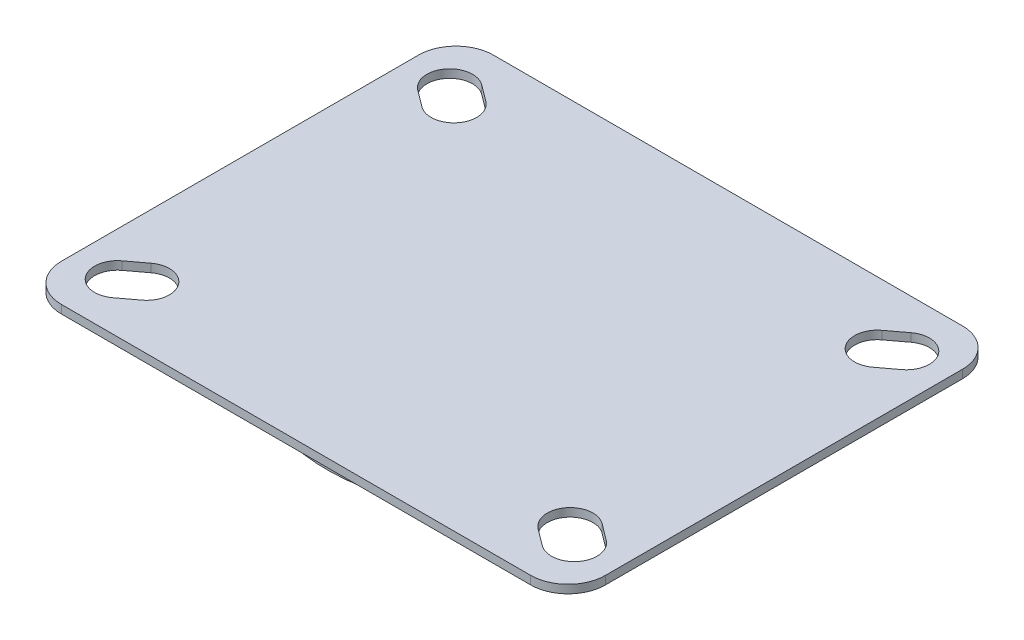
SolidWorks part; units mm, degrees
material "Acero al carbono no aleado"
ref_plane "Alzado" through (0, 0, 0) normal (0, 0, 1) x (1, 0, 0)
ref_plane "Planta" through (0, 0, 0) normal (0, 1, 0) x (1, 0, 0)
ref_plane "Vista lateral" through (0, 0, 0) normal (1, 0, 0) x (0, 0, -1)
sketch "Croquis1" plane through (0, 0, 0) normal (0, 1, 0) x (1, 0, 0)
  line L0 (-54.9902, 40) -> (-50.9902, 37) construction
  line L1 (-56.4956, -52) -> (56.4956, -52)
  line L2 (-65.5, -42.9956) -> (-65.5, 42.9956)
  line L3 (-56.4956, 52) -> (56.4956, 52)
  line L4 (65.5, -42.9956) -> (65.5, 42.9956)
  line L5 (-65.5, -52) -> (65.5, 52) construction
  line L6 (-65.5, 52) -> (65.5, -52) construction
  line L7 (-51.6902, 44.4) -> (-47.6902, 41.4)
  line L8 (-58.2902, 35.6) -> (-54.2902, 32.6)
  line L9 (0, 69.9455) -> (0, -63.4447) construction
  line L10 (-82.1869, 0) -> (96.8414, 0) construction
  line L11 (54.9902, 40) -> (50.9902, 37) construction
  line L12 (51.6902, 44.4) -> (47.6902, 41.4)
  line L13 (58.2902, 35.6) -> (54.2902, 32.6)
  line L14 (-54.9902, -40) -> (-50.9902, -37) construction
  line L15 (-51.6902, -44.4) -> (-47.6902, -41.4)
  line L16 (-58.2902, -35.6) -> (-54.2902, -32.6)
  line L17 (54.9902, -40) -> (50.9902, -37) construction
  line L18 (51.6902, -44.4) -> (47.6902, -41.4)
  line L19 (58.2902, -35.6) -> (54.2902, -32.6)
  circle A0 centre (0, 0) radius 40 construction
  arc A1 (-51.6902, 44.4) -> (-58.2902, 35.6) centre (-54.9902, 40) ccw
  arc A2 (-54.2902, 32.6) -> (-47.6902, 41.4) centre (-50.9902, 37) ccw
  arc A3 (51.6902, 44.4) -> (58.2902, 35.6) centre (54.9902, 40) cw
  arc A4 (54.2902, 32.6) -> (47.6902, 41.4) centre (50.9902, 37) cw
  arc A5 (-51.6902, -44.4) -> (-58.2902, -35.6) centre (-54.9902, -40) cw
  arc A6 (-54.2902, -32.6) -> (-47.6902, -41.4) centre (-50.9902, -37) cw
  arc A7 (51.6902, -44.4) -> (58.2902, -35.6) centre (54.9902, -40) ccw
  arc A8 (54.2902, -32.6) -> (47.6902, -41.4) centre (50.9902, -37) ccw
  arc A9 (-56.4956, -52) -> (-65.5, -42.9956) centre (-56.4956, -42.9956) cw
  arc A10 (56.4956, -52) -> (65.5, -42.9956) centre (56.4956, -42.9956) ccw
  arc A11 (56.4956, 52) -> (65.5, 42.9956) centre (56.4956, 42.9956) cw
  arc A12 (-65.5, 42.9956) -> (-56.4956, 52) centre (-56.4956, 42.9956) cw
  point P0 (0, 0)
  point P10 (-52.9902, 38.5)
  point P21 (52.9902, 38.5)
  point P28 (-52.9902, -38.5)
  point P35 (52.9902, -38.5)
  dimension "D3" = 80
  dimension "D5" = 115
  dimension "D6" = 16
  dimension "D7" = 63
  dimension "D8" = 91
  dimension "D9" = 160
  dimension "D1" = 131
  dimension "D2" = 104
  dimension "D4" = 11
base flange "Brida base1" sketch "Croquis1" thickness 2 reverse thickness direction no parameters "D1"=1
sketch "Croquis6" plane through (0, -2, 0) normal (0, 1, 0) x (1, 0, 0)
  circle A0 centre (0, 0) radius 42.5
  dimension "D1" = 85
extrude "Extruir-Lámina1" add sketch "Croquis6" against normal blind 8 separate body thin thin type one direction wall 2
sketch "Líneas de pliegue1" [suppressed] plane through (0, 0, 0) normal (0, 1, 0) x (1, 0, 0)
sketch "Cuadro delimitador1" [suppressed] plane through (0, 0, 0) normal (0, 1, 0) x (1, 0, 0)
sheet metal parameters "Chapa metálica1" thickness 2 parameters "D1"=1
flat pattern "Chapa desplegada1" [suppressed]
sketch "Líneas de pliegue2" plane through (0, 0, 0) normal (0, 1, 0) x (1, 0, 0)
sketch3d "Cuadro delimitador2" [suppressed]
  line L0 (9.0044, 94.9956, 0) -> (-121.9956, 94.9956, 0) construction
  line L1 (9.0044, -9.0044, 0) -> (-121.9956, -9.0044, 0) construction
  line L2 (9.0044, 94.9956, 0) -> (9.0044, -9.0044, 0) construction
  line L3 (-121.9956, 94.9956, 0) -> (-121.9956, -9.0044, 0) construction
